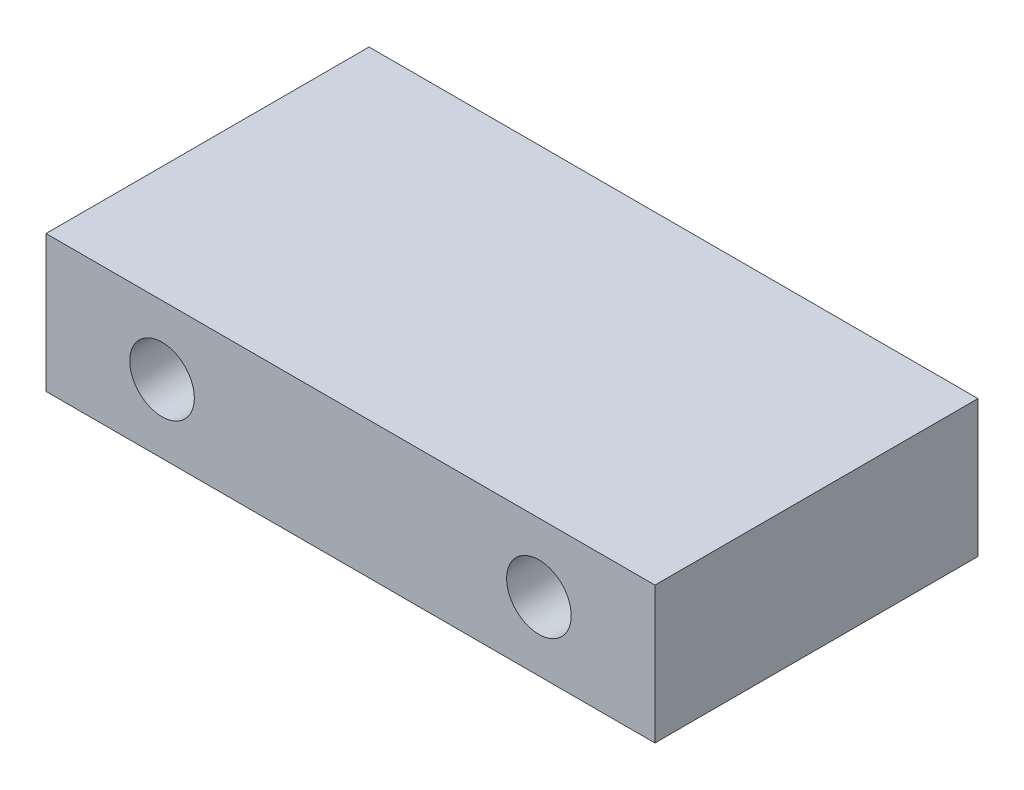
SolidWorks part; units mm, degrees
material "6061-T6 (SS)"
ref_plane "X-Y Datum" through (0, 0, 0) normal (0, 0, 1) x (1, 0, 0)
ref_plane "X-Z Datum" through (0, 0, 0) normal (0, 1, 0) x (1, 0, 0)
ref_plane "Y-Z Datum" through (0, 0, 0) normal (1, 0, 0) x (0, 0, -1)
sketch "Sketch1" plane through (0, 0, 0) normal (0, 0, 1) x (1, 0, 0)
  line L1 (-28.275, 6.35) -> (28.275, 6.35)
  line L2 (-28.275, 6.35) -> (-28.275, -6.35)
  line L3 (-28.275, -6.35) -> (28.275, -6.35)
  line L4 (28.275, 6.35) -> (28.275, -6.35)
  line L5 (-28.275, 6.35) -> (28.275, -6.35) construction
  line L6 (-28.275, -6.35) -> (28.275, 6.35) construction
  point P0 (0, 0)
  dimension "D1" = 56.55
  dimension "D2" = 12.7
extrude "Boss-Extrude1" add sketch "Sketch1" along normal blind 30 contours L2 L3 L4 L1
sketch "Sketch2" plane through (0, 0, 30) normal (0, 0, 1) x (1, 0, 0)
  line L0 (-28.275, 0) -> (28.275, 0) construction
  line L1 (-28.275, 6.35) -> (-28.275, -6.35) construction
  line L2 (28.275, 6.35) -> (28.275, -6.35) construction
  line L3 (-17.5, 0) -> (17.5, 0) construction
  circle A0 centre (17.5, 0) radius 3
  circle A1 centre (-17.5, 0) radius 3
  point P10 (0, 0)
  dimension "D1" = 6
  dimension "D2" = 35
extrude "Cut-Extrude1" cut sketch "Sketch2" against normal blind 12 contours A1 L0 L3 | L0 A1 L3 | L0 L3 A0 | L3 L0 A0 region at (17.5, 0, 30) region at (-17.5, 0, 30)
